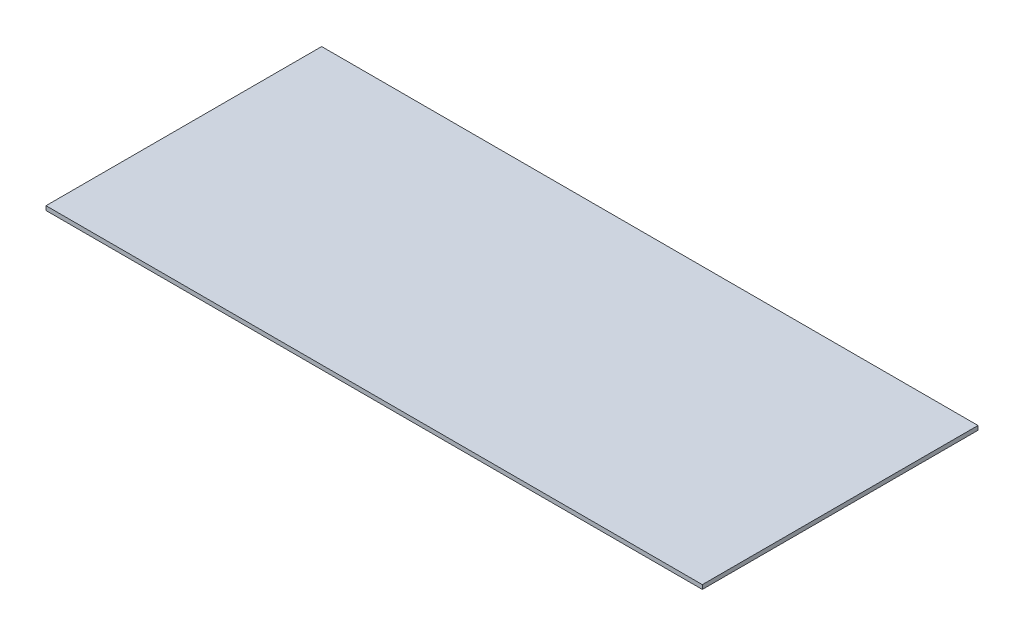
SolidWorks part; units mm, degrees
ref_plane "Front" through (0, 0, 0) normal (0, 0, 1) x (1, 0, 0)
ref_plane "Top" through (0, 0, 0) normal (0, 1, 0) x (1, 0, 0)
ref_plane "Right" through (0, 0, 0) normal (1, 0, 0) x (0, 0, -1)
sketch "Esquisse1" plane through (0, 0, 0) normal (0, 1, 0) x (1, 0, 0)
  line L1 (0, 0) -> (2500, 0)
  line L2 (0, 0) -> (0, 1050)
  line L3 (0, 1050) -> (2500, 1050)
  line L4 (2500, 0) -> (2500, 1050)
  dimension "D1" = 2500
  dimension "D2" = 1050
extrude "Boss.-Extru.1" add sketch "Esquisse1" along normal blind 16
